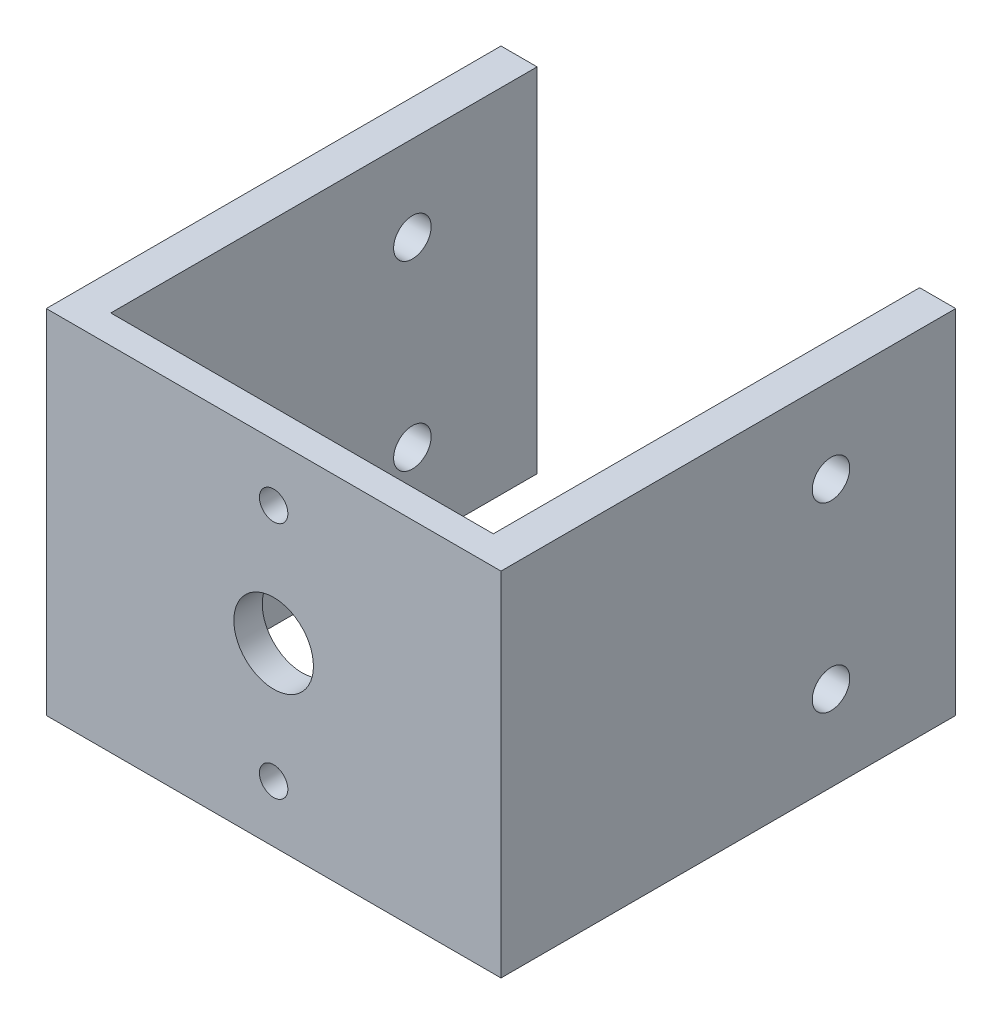
SolidWorks part; units mm, degrees
ref_plane "Front Plane" through (0, 0, 0) normal (0, 0, 1) x (1, 0, 0)
ref_plane "Top Plane" through (0, 0, 0) normal (0, 1, 0) x (1, 0, 0)
ref_plane "Right Plane" through (0, 0, 0) normal (1, 0, 0) x (0, 0, -1)
sketch "Sketch3" plane through (0, 0, 0) normal (0, 0, 1) x (1, 0, 0)
  line L1 (-20, 0) -> (20, 0)
  line L2 (-20, 0) -> (-20, 31)
  line L3 (-20, 31) -> (20, 31)
  line L4 (20, 0) -> (20, 31)
  line L5 (-16.825, 0) -> (16.825, 0)
  line L6 (-16.825, 0) -> (-16.825, 31)
  line L7 (-16.825, 31) -> (16.825, 31)
  line L8 (16.825, 0) -> (16.825, 31)
  circle A0 centre (0, 15.5) radius 3.5
  circle A1 centre (0, 26) radius 1.25
  circle A2 centre (0, 5) radius 1.25
  circle A3 centre (0, 15.5) radius 12.5 construction
  point P4 (0, 0)
  point P18 (0, 0)
  dimension "D2" = 7
  dimension "D3" = 2.5
  dimension "D6" = 25
  dimension "D1" = 40
  dimension "D4" = 21
  dimension "D5" = 10.5
  dimension "D7" = 5
  dimension "D8" = 5
  dimension "D9" = 3.175
  dimension "D10" = 3.175
extrude "Boss-Extrude3" add sketch "Sketch3" against normal blind 2.5 contours L1 L8 L3 L6 A2 A1 A0 region at (-16.3675, 15.5, 0)
extrude "Boss-Extrude4" add sketch "Sketch3<3>" against normal blind 40 contours L1 L6 L3 L2 | L8 L1 L4 L3 region at (-18.4125, 15.5, 0) region at (18.4125, 15.5, 0)
sketch "Sketch3<3>" plane through (0, 0, 0) normal (0, 0, 1) x (1, 0, 0) same geometry as "Sketch3"
sketch "Sketch4" plane through (-20, 0, 0) normal (-1, 0, 0) x (0, 0, 1)
  line L0 (-29.03, 7.5) -> (-29.03, 23.5) construction
  line L1 (-40, 0) -> (-40, 31) construction
  line L2 (0, 0) -> (0, 31) construction
  circle A0 centre (-29.03, 23.5) radius 1.65
  circle A1 centre (-29.03, 7.5) radius 1.65
  point P6 (-40, 15.5)
  point P7 (-29.03, 15.5)
  point P8 (-20.9465, 9.175)
  dimension "D1" = 3.3
  dimension "D2" = 16
  dimension "D3" = 29.03
extrude "Cut-Extrude1" cut sketch "Sketch4" against normal up to surface (40 mm away) up to face at (20, 15.5, -20)
